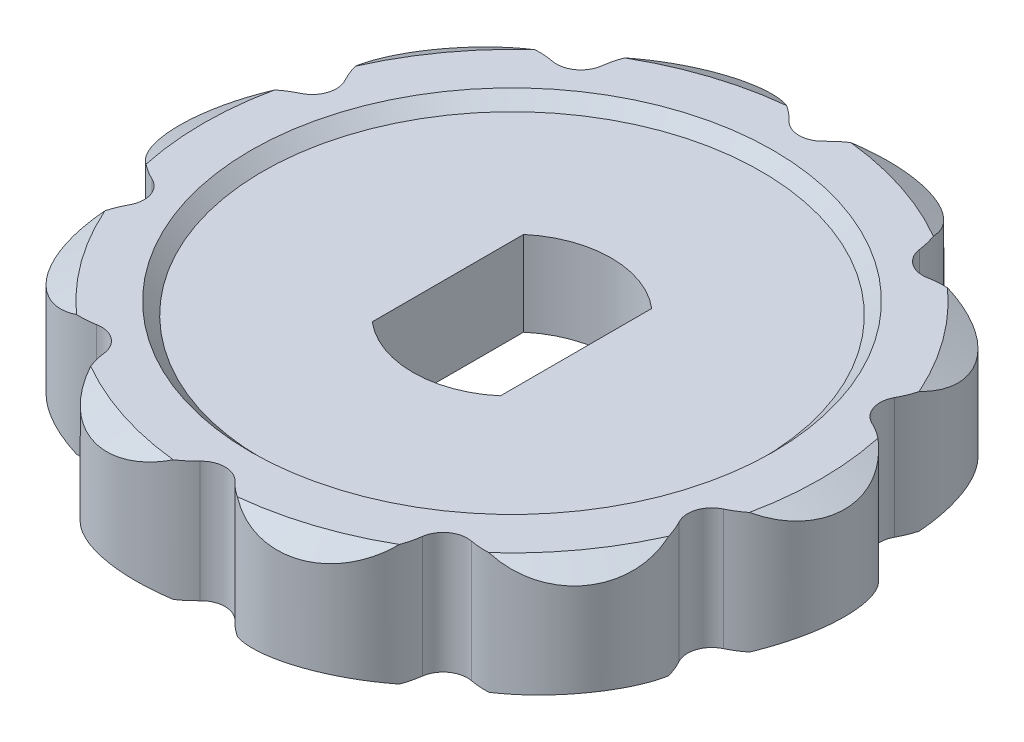
SolidWorks part; units mm, degrees
material "1023 Carbon Steel Sheet (SS)"
ref_plane "Front Plane" through (0, 0, 0) normal (0, 0, 1) x (1, 0, 0)
ref_plane "Top Plane" through (0, 0, 0) normal (0, 1, 0) x (1, 0, 0)
ref_plane "Right Plane" through (0, 0, 0) normal (1, 0, 0) x (0, 0, -1)
sketch "Sketch1" plane through (0, 0, 0) normal (0, 1, 0) x (1, 0, 0)
  line L0 (0, 0) -> (0, 18.0517) construction
  line L1 (0, 0) -> (6.4656, 8.8992) construction
  line L2 (0, 0) -> (3.3992, 10.4616) construction
  line L4 (4.249, 13.077) -> (6.1506, 18.9296) construction
  circle A0 centre (0, 0) radius 13.75 construction
  circle A1 centre (0, 0) radius 11 construction
  arc A2 (0, 11) -> (6.4656, 8.8992) centre (3.198, 9.8424) cw
  arc A3 (6.4656, 8.8992) -> (10.4616, 3.3992) centre (8.3725, 6.083) cw
  arc A4 (10.4616, 3.3992) -> (10.4616, -3.3992) centre (10.3489, 0) cw
  arc A5 (10.4616, -3.3992) -> (6.4656, -8.8992) centre (8.3725, -6.083) cw
  arc A6 (6.4656, -8.8992) -> (0, -11) centre (3.198, -9.8424) cw
  arc A7 (0, -11) -> (-6.4656, -8.8992) centre (-3.198, -9.8424) cw
  arc A8 (-6.4656, -8.8992) -> (-10.4616, -3.3992) centre (-8.3725, -6.083) cw
  arc A9 (-10.4616, -3.3992) -> (-10.4616, 3.3992) centre (-10.3489, 0) cw
  arc A10 (-10.4616, 3.3992) -> (-6.4656, 8.8992) centre (-8.3725, 6.083) cw
  arc A11 (-6.4656, 8.8992) -> (0, 11) centre (-3.198, 9.8424) cw
  point P41 (0, 0)
  dimension "D1" = 27.5
  dimension "D2" = 22
  dimension "D3" = 36
  dimension "D4" = 18
  dimension "D5" = 10
extrude "Boss-Extrude1" add sketch "Sketch1" along normal blind 5
fillet "Fillet2" radius 1 10 edges at (10.4616, 2.5, 3.3992) (6.4656, 2.5, 8.8992) (0, 2.5, 11) (-6.4656, 2.5, 8.8992) (-10.4616, 2.5, 3.3992) (-10.4616, 2.5, -3.3992) (-6.4656, 2.5, -8.8992) (0, 2.5, -11) (6.4656, 2.5, -8.8992) (10.4616, 2.5, -3.3992)
sketch "Sketch5" plane through (0, 5, 0) normal (0, 1, 0) x (1, 0, 0)
  circle A0 centre (0, 0) radius 10.3
  dimension "D1" = 20.6
extrude "Cut-Extrude1" cut sketch "Sketch5" against normal blind 0.5
chamfer "Chamfer1" distance 0.5 1 edges at (0, 5, 10.3)
sketch "Sketch6" plane through (0, 5, 0) normal (0, 1, 0) x (1, 0, 0)
  circle A0 centre (0, 0) radius 12.75
  dimension "D1" = 25.5
extrude "Cut-Extrude2" cut sketch "Sketch6" against normal blind 100.2 draft 60 flip side to cut
sketch "Sketch7" plane through (0, 0, 0) normal (0, -1, 0) x (1, 0, 0)
  circle A0 centre (0, 0) radius 12.75
  dimension "D1" = 25.5
extrude "Cut-Extrude3" cut sketch "Sketch7" against normal blind 40.5 draft 60 flip side to cut
sketch "Sketch8" plane through (0, 4.5, 0) normal (0, 1, 0) x (1, 0, 0)
  line L2 (-2.65, -3.1285) -> (-2.65, 3.1285)
  line L4 (2.65, -3.1285) -> (2.65, 3.1285)
  arc A0 (2.65, 3.1285) -> (-2.65, 3.1285) centre (0, 0) ccw
  arc A1 (-2.65, -3.1285) -> (2.65, -3.1285) centre (0, 0) ccw
  dimension "D1" = 5.3
  dimension "D4" = 2.65
extrude "Cut-Extrude4" cut sketch "Sketch8" against normal blind 40.5
sketch "Sketch9" plane through (0, 0, 0) normal (0, -1, 0) x (1, 0, 0)
  circle A0 centre (0, 0) radius 11.4
  circle A1 centre (0, 0) radius 5.625
  dimension "D1" = 22.8
  dimension "D2" = 11.25
extrude "Cut-Extrude5" cut sketch "Sketch9" against normal blind 3.4
sketch "Sketch10" plane through (0, 0, 0) normal (0, -1, 0) x (1, 0, 0)
  circle A0 centre (0, 0) radius 6
extrude "Cut-Extrude6" cut sketch "Sketch10" against normal blind 1
